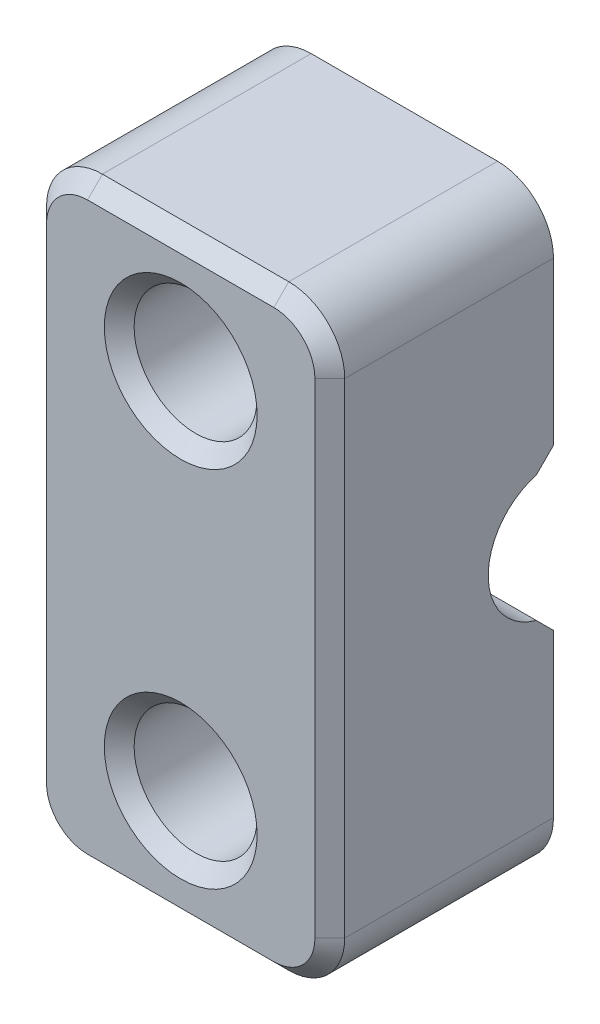
SolidWorks part; units mm, degrees
ref_plane "Front Plane" through (0, 0, 0) normal (0, 0, 1) x (1, 0, 0)
ref_plane "Top Plane" through (0, 0, 0) normal (0, 1, 0) x (1, 0, 0)
ref_plane "Right Plane" through (0, 0, 0) normal (1, 0, 0) x (0, 0, -1)
sketch "Sketch2" plane through (0, 0, 0) normal (0, 0, 1) x (1, 0, 0)
  line L1 (-4, 8) -> (4, 8)
  line L2 (-4, 8) -> (-4, -8)
  line L3 (-4, -8) -> (4, -8)
  line L4 (4, 8) -> (4, -8)
  line L5 (-4, 8) -> (4, -8) construction
  line L6 (-4, -8) -> (4, 8) construction
  point P0 (0, 0)
  dimension "D1" = 16
  dimension "D2" = 8
extrude "Boss-Extrude1" add sketch "Sketch2" along normal blind 6
sketch "Sketch3" plane through (-4, 0, 0) normal (-1, 0, 0) x (0, 0, 1)
  line L0 (0, 8) -> (0, -8) construction
  line L1 (0, -1.75) -> (0, 1.75)
  circle A0 centre (0, 0) radius 1.75
  line M2 (0, 8) -> (0, -8)
  dimension "D1" = 3.5
extrude "Cut-Extrude1" cut sketch "Sketch3" against normal blind 8 contours A0 M2 | A0 M2 region at (-4, 0, -0.7427) region at (-4, 0, 0.7427)
sketch "Sketch4" plane through (0, 0, 0) normal (0, 0, -1) x (-1, 0, 0)
  line L0 (0, 8) -> (0, 1.75) construction
  line L1 (-4, 8) -> (4, 8) construction
  line L2 (-4, 1.75) -> (4, 1.75) construction
  line L3 (0, -1.75) -> (0, -8) construction
  line L4 (4, -1.75) -> (-4, -1.75) construction
  line L5 (4, -8) -> (-4, -8) construction
  circle A0 centre (0, -4.875) radius 1.65
  circle A1 centre (0, 4.875) radius 1.65
  dimension "D1" = 3.3
  dimension "D2" = 3.3
extrude "Cut-Extrude2" cut sketch "Sketch4" against normal blind 6
fillet "Fillet1" radius 1.5 4 edges at (4, -8, 3) (-4, -8, 3) (-4, 8, 3) (4, 8, 3)
chamfer "Chamfer1" distance 0.4 angle 45 10 edges at (-1.65, 4.875, 6) (-1.65, -4.875, 6) (-4, 0, 6) (-3.5607, -7.5607, 6) (-3.5607, 7.5607, 6) (0, -8, 6) (0, 8, 6) (3.5607, -7.5607, 6) (3.5607, 7.5607, 6) (4, 0, 6)
chamfer "Chamfer2" distance 0.4 angle 45 2 edges at (0, 1.75, 0) (0, -1.75, 0)
